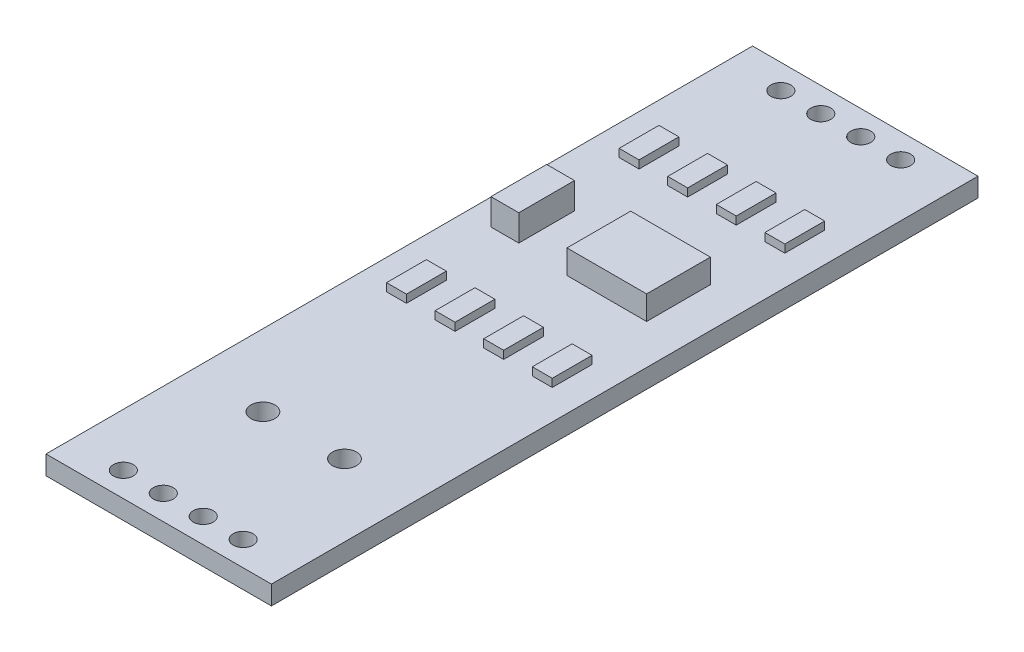
SolidWorks part; units mm, degrees
ref_plane "Front Plane" through (0, 0, 0) normal (0, 0, 1) x (1, 0, 0)
ref_plane "Top Plane" through (0, 0, 0) normal (0, 1, 0) x (1, 0, 0)
ref_plane "Right Plane" through (0, 0, 0) normal (1, 0, 0) x (0, 0, -1)
sketch "Sketch1" plane through (0, 0, 0) normal (0, 1, 0) x (1, 0, 0)
  line L1 (-7.075, -22.175) -> (7.075, -22.175)
  line L2 (-7.075, -22.175) -> (-7.075, 22.175)
  line L3 (-7.075, 22.175) -> (7.075, 22.175)
  line L4 (7.075, -22.175) -> (7.075, 22.175)
  line L5 (-7.075, -22.175) -> (7.075, 22.175) construction
  line L6 (-7.075, 22.175) -> (7.075, -22.175) construction
  point P0 (0, 0)
  dimension "D1" = 14.15
  dimension "D2" = 44.35
extrude "Boss-Extrude1" add sketch "Sketch1" along normal blind 1.19
sketch "Sketch2" plane through (0, 1.19, 0) normal (0, 1, 0) x (1, 0, 0)
  line L0 (-7.075, -22.175) -> (7.075, -22.175) construction
  line L1 (3.76, -20.635) -> (1.2533, -20.635) construction
  line L2 (1.2533, -20.635) -> (-1.2533, -20.635) construction
  line L3 (-1.2533, -20.635) -> (-3.76, -20.635) construction
  circle A0 centre (3.76, -20.635) radius 0.625
  circle A1 centre (1.2533, -20.635) radius 0.625
  circle A2 centre (-1.2533, -20.635) radius 0.625
  circle A3 centre (-3.76, -20.635) radius 0.625
  point P5 (0, -20.635)
  point P12 (0, 0)
  point P14 (-3.76, -20.7216)
  dimension "D3" = 1.25
  dimension "D1" = 7.52
  dimension "D2" = 1.54
extrude "Cut-Extrude1" cut sketch "Sketch2" against normal through all
mirror "Mirror1" about plane through (0, 0, 0) normal (0, 0, 1) of "Cut-Extrude1"
sketch "Sketch3" plane through (0, 1.19, 0) normal (0, 1, 0) x (1, 0, 0)
  line L0 (-2.56, -13.075) -> (2.56, -13.075) construction
  line L1 (-7.075, -22.175) -> (7.075, -22.175) construction
  circle A0 centre (2.56, -13.075) radius 0.75
  circle A1 centre (-2.56, -13.075) radius 0.75
  point P2 (0, -13.075)
  dimension "D3" = 1.5
  dimension "D1" = 5.12
  dimension "D2" = 9.1
extrude "Cut-Extrude2" cut sketch "Sketch3" against normal through all
sketch "Sketch4" plane through (0, 1.19, 0) normal (0, 1, 0) x (1, 0, 0)
  line L0 (7.075, -22.175) -> (7.075, 22.175) construction
  line L1 (-0.425, 7.875) -> (4.575, 7.875)
  line L2 (-0.425, 7.875) -> (-0.425, 3.875)
  line L3 (-0.425, 3.875) -> (4.575, 3.875)
  line L4 (4.575, 7.875) -> (4.575, 3.875)
  line L5 (-0.425, 7.875) -> (4.575, 3.875) construction
  line L6 (-0.425, 3.875) -> (4.575, 7.875) construction
  line L7 (-5.45, 7.625) -> (-3.7, 7.625)
  line L8 (-5.45, 7.625) -> (-5.45, 4.125)
  line L9 (-5.45, 4.125) -> (-3.7, 4.125)
  line L10 (-3.7, 7.625) -> (-3.7, 4.125)
  line L11 (-5.45, 7.625) -> (-3.7, 4.125) construction
  line L12 (-5.45, 4.125) -> (-3.7, 7.625) construction
  line L13 (7.075, 22.175) -> (-7.075, 22.175) construction
  line L14 (-7.075, 22.175) -> (-7.075, -22.175) construction
  point P0 (2.075, 5.875)
  point P5 (-4.575, 5.875)
  dimension "D1" = 1.75
  dimension "D2" = 3.5
  dimension "D3" = 5
  dimension "D4" = 4
  dimension "D5" = 5
  dimension "D6" = 16.3
  dimension "D7" = 2.5
  dimension "D8" = 16.3
extrude "Boss-Extrude2" add sketch "Sketch4" along normal blind 1.5 contours L4 L1 L2 L3 region at (2.075, 1.19, -5.875)
extrude "Boss-Extrude3" add sketch "Sketch4<3>" along normal blind 1.65 contours L10 L7 L8 L9 region at (-4.575, 1.19, -5.875)
sketch "Sketch4<3>" plane through (0, 1.19, 0) normal (0, 1, 0) x (1, 0, 0) same geometry as "Sketch4"
ref_plane "Plane1" through (0, 0, -5.875) normal (0, 0, 1) x (1, 0, 0)
sketch "Sketch7" plane through (0, 1.19, 0) normal (0, 1, 0) x (1, 0, 0)
  line L0 (-3.95, -2.675) -> (-2.15, -2.675) construction
  line L1 (-5.2, -0.175) -> (-3.95, -0.175)
  line L2 (-5.2, -0.175) -> (-5.2, -2.675)
  line L3 (-5.2, -2.675) -> (-3.95, -2.675)
  line L4 (-3.95, -0.175) -> (-3.95, -2.675)
  line L5 (-2.15, -0.175) -> (-0.9, -0.175)
  line L6 (-2.15, -0.175) -> (-2.15, -2.675)
  line L7 (-2.15, -2.675) -> (-0.9, -2.675)
  line L8 (-0.9, -0.175) -> (-0.9, -2.675)
  line L9 (0.9, -0.175) -> (2.15, -0.175)
  line L10 (0.9, -0.175) -> (0.9, -2.675)
  line L11 (0.9, -2.675) -> (2.15, -2.675)
  line L12 (2.15, -0.175) -> (2.15, -2.675)
  line L13 (3.95, -0.175) -> (5.2, -0.175)
  line L14 (3.95, -0.175) -> (3.95, -2.675)
  line L15 (3.95, -2.675) -> (5.2, -2.675)
  line L16 (5.2, -0.175) -> (5.2, -2.675)
  line L17 (-0.9, -2.675) -> (0.9, -2.675) construction
  line L18 (2.15, -2.675) -> (3.95, -2.675) construction
  line L19 (-7.075, -22.175) -> (7.075, -22.175) construction
  point P16 (-1.525, -0.175)
  point P17 (0, -2.675)
  dimension "D1" = 1.25
  dimension "D2" = 2.5
  dimension "D3" = 10.4
  dimension "D4" = 22
extrude "Boss-Extrude6" add sketch "Sketch7" along normal blind 0.5
mirror "Mirror2" about plane through (0, 0, -5.875) normal (0, 0, 1) of "Boss-Extrude6"
